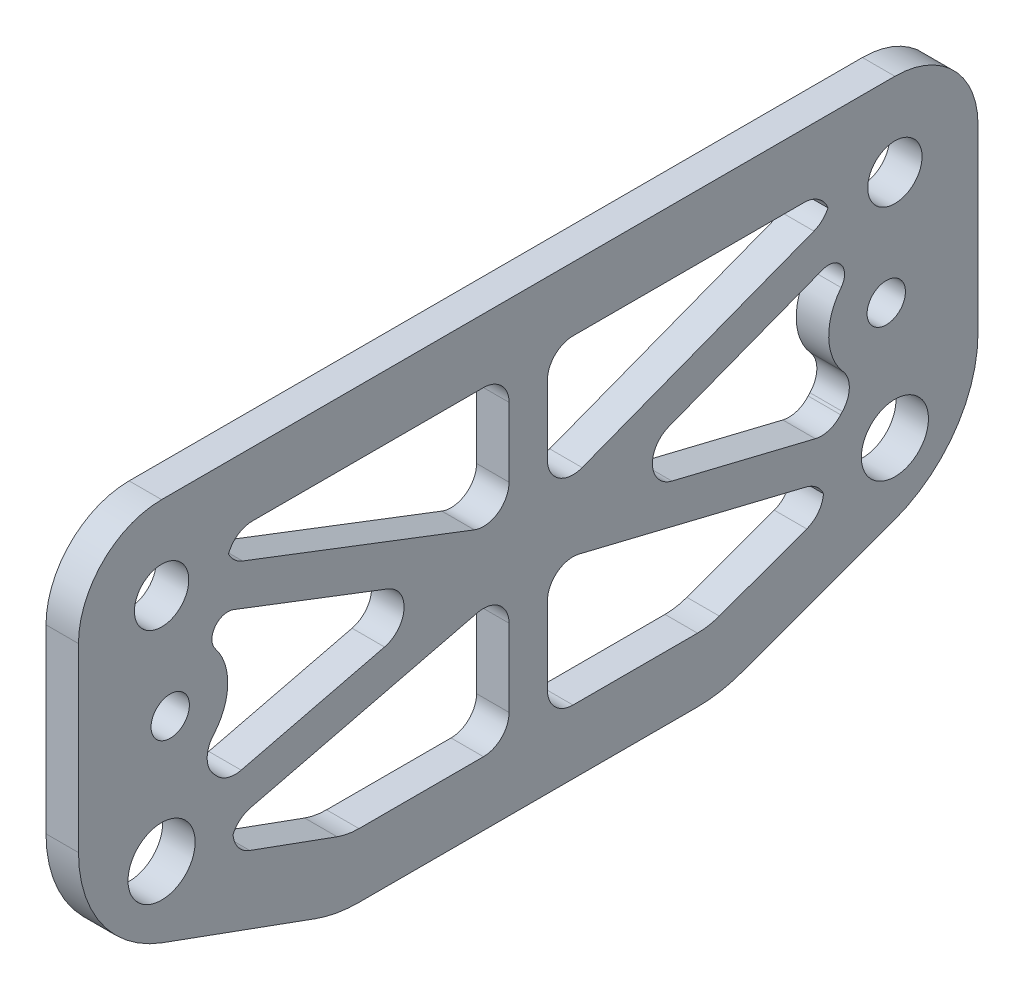
SolidWorks part; units mm, degrees
material "Acrylic (Medium-high impact)"
ref_plane "Front Plane" through (0, 0, 0) normal (0, 0, 1) x (1, 0, 0)
ref_plane "Top Plane" through (0, 0, 0) normal (0, 1, 0) x (1, 0, 0)
ref_plane "Right Plane" through (0, 0, 0) normal (1, 0, 0) x (0, 0, -1)
sketch "Sketch1" plane through (0, 0, 0) normal (1, 0, 0) x (0, 0, -1)
  line L0 (15, 17.5) -> (28.675, 17.5)
  line L1 (-15, -17.5) -> (15, -17.5)
  line L3 (-15, 17.5) -> (15, 17.5)
  line L5 (-15, -17.5) -> (15, 17.5) construction
  line L6 (-15, 17.5) -> (15, -17.5) construction
  line L8 (0, 17.5) -> (0, -17.5) construction
  line L10 (-15, 17.5) -> (-28.675, 17.5)
  line L11 (23.175, 171.1912) -> (23.175, -56.2088) construction
  line L13 (35.175, 11) -> (35.175, -3.1548)
  line L14 (28.5952, -12.5518) -> (15, -17.5)
  line L16 (-35.175, 11) -> (-35.175, -3.1548)
  line L17 (-28.5952, -12.5518) -> (-15, -17.5)
  arc A0 (28.675, 17.5) -> (35.175, 11) centre (28.675, 11) cw
  circle A1 centre (28.675, 11) radius 5.5 construction
  circle A2 centre (-28.675, 11) radius 5.5 construction
  arc A3 (-28.675, 17.5) -> (-35.175, 11) centre (-28.675, 11) ccw
  arc A4 (35.175, -3.1548) -> (28.5952, -12.5518) centre (25.175, -3.1548) cw
  circle A5 centre (28.675, 11) radius 2.125
  arc A6 (-35.175, -3.1548) -> (-28.5952, -12.5518) centre (-25.175, -3.1548) ccw
  circle A9 centre (-28.675, 11) radius 2.125
  circle A11 centre (28, 2.5) radius 1.5
  circle A12 centre (-28, 2.5) radius 1.5
  circle A13 centre (28.675, -7) radius 5.5 construction
  circle A14 centre (28.675, -7) radius 2.625
  circle A15 centre (-28.675, -7) radius 2.625
  circle A16 centre (-28.675, -7) radius 5.5 construction
  point P0 (0, 0)
  point P28 (0, 0)
  dimension "D1" = 11
  dimension "D2" = 1
  dimension "D3" = 4.25
  dimension "D4" = 3
  dimension "D6" = 20
  dimension "D8" = 10
  dimension "D11" = 5.25
  dimension "D12" = 11
  dimension "D5" = 35
  dimension "D7" = 30
  dimension "D9" = 28
  dimension "D10" = 8.5
  dimension "D13" = 9.5
extrude "Boss-Extrude1" add sketch "Sketch1" along normal blind 2.54
fillet "Fillet1" radius 10 2 edges at (1.27, -17.5, -15) (1.27, -17.5, 15)
sketch "Sketch2" plane through (0, 0, 0) normal (1, 0, 0) x (0, 0, -1)
  line L0 (-28.675, 11) -> (0, 0)
  line L5 (0, 12.5) -> (0, -12.5) construction
  line L7 (-28, 2.5) -> (0, 0)
  line L8 (0, 17.5) -> (0, -17.5) construction
  line L9 (-28.675, -7) -> (0, 0)
  line L10 (-29.0307, -5.5428) -> (-0.3557, 1.4572)
  line L11 (-28.3193, -8.4572) -> (0.3557, -1.4572)
  line L16 (-13.2367, -12.5) -> (13.2367, -12.5)
  line L17 (14.9468, -12.1985) -> (26.8851, -7.8533)
  line L18 (30.175, -3.1548) -> (30.175, 11)
  line L19 (28.675, 12.5) -> (-28.675, 12.5)
  line L20 (-30.175, 11) -> (-30.175, -3.1548)
  line L21 (-26.8851, -7.8533) -> (-14.9468, -12.1985)
  line L22 (-13.2367, -12.5) -> (13.2367, -12.5)
  line L23 (14.9468, -12.1985) -> (26.8851, -7.8533)
  line L24 (30.175, -3.1548) -> (30.175, 11)
  line L25 (28.675, 12.5) -> (-28.675, 12.5)
  line L26 (-30.175, 11) -> (-30.175, -3.1548)
  line L27 (-26.8851, -7.8533) -> (-14.9468, -12.1985)
  line L32 (0, -12.5) -> (0, 12.5) construction
  line L33 (0, 0) -> (0, -12.5)
  line L34 (-1.5, 12.5) -> (-1.5, -12.5)
  line L35 (1.5, 12.5) -> (1.5, -12.5)
  line L36 (-1.5, 12.5) -> (1.5, 12.5)
  line L37 (-1.5, -12.5) -> (1.5, -12.5)
  line L38 (-29.2122, 9.5995) -> (-0.5372, -1.4005)
  line L39 (-28.1378, 12.4005) -> (0.5372, 1.4005)
  line L40 (28.675, -7) -> (0, 0)
  line L41 (28.3193, -8.4572) -> (-0.3557, -1.4572)
  line L42 (28.1378, 12.4005) -> (-0.5372, 1.4005)
  line L43 (29.0307, -5.5428) -> (0.3557, 1.4572)
  line L44 (29.2122, 9.5995) -> (0.5372, -1.4005)
  line L45 (28.675, 11) -> (0, 0)
  arc A1 (23.0409, 7.2321) -> (24.4693, 5.29) centre (23.4886, 6.065) cw
  circle A2 centre (-28, 2.5) radius 4.5
  circle A3 centre (-28, 2.5) radius 4.5
  arc A4 (-23.0409, 7.2321) -> (-24.4693, 5.29) centre (-23.4886, 6.065) ccw
  circle A5 centre (28, 2.5) radius 4.5
  circle A6 centre (28, 2.5) radius 4.5
  circle A10 centre (28.675, -7) radius 5.625
  circle A11 centre (-28.675, 11) radius 5.125
  arc A12 (13.2367, -12.5) -> (14.9468, -12.1985) centre (13.2367, -7.5) ccw
  arc A13 (26.8851, -7.8533) -> (30.175, -3.1548) centre (25.175, -3.1548) ccw
  arc A14 (30.175, 11) -> (28.675, 12.5) centre (28.675, 11) ccw
  arc A15 (-28.675, 12.5) -> (-30.175, 11) centre (-28.675, 11) ccw
  arc A16 (-30.175, -3.1548) -> (-26.8851, -7.8533) centre (-25.175, -3.1548) ccw
  arc A17 (-14.9468, -12.1985) -> (-13.2367, -12.5) centre (-13.2367, -7.5) ccw
  arc A18 (13.2367, -12.5) -> (14.9468, -12.1985) centre (13.2367, -7.5) ccw
  arc A19 (26.8851, -7.8533) -> (30.175, -3.1548) centre (25.175, -3.1548) ccw
  arc A20 (30.175, 11) -> (28.675, 12.5) centre (28.675, 11) ccw
  arc A21 (-28.675, 12.5) -> (-30.175, 11) centre (-28.675, 11) ccw
  arc A22 (-30.175, -3.1548) -> (-26.8851, -7.8533) centre (-25.175, -3.1548) ccw
  arc A23 (-14.9468, -12.1985) -> (-13.2367, -12.5) centre (-13.2367, -7.5) ccw
  circle A24 centre (-28.675, 11) radius 5.125
  circle A25 centre (28.675, -7) radius 5.625
  circle A26 centre (28.675, 11) radius 5.125
  circle A27 centre (28.675, 11) radius 5.125
  circle A31 centre (-28.675, -7) radius 5.625
  circle A32 centre (-28.675, -7) radius 5.625
  dimension "D10" = 1.5
  dimension "D11" = 3
  dimension "D12" = 1.25
  dimension "D1" = 5
  dimension "D3" = 3
  dimension "D4" = 3
  dimension "D5" = 3
  dimension "D6" = 3
  dimension "D7" = 1.5
  dimension "D8" = 1.5
  dimension "D9" = 1.5
  dimension "D13" = 1.5
  dimension "D14" = 1.5
  dimension "D15" = 3
extrude "Cut-Extrude2" cut sketch "Sketch2" along normal through all contours A25 L41 L35 L22 A18 L23 | A32 L27 A23 L22 L34 L11 | A27 L44 L43 A25 A6 | A24 A3 L7 L38 | A32 L10 L38 L7 A3 | A24 L39 L34 L25 | A27 L25 L35 L42
fillet "Fillet2" radius 2 22 edges at (1.27, -12.5, -1.5) (1.27, -12.5, 1.5) (1.27, -1.9102, -1.5) (1.27, -9.101, -23.4571) (1.27, -7.1715, -23.0526) (1.27, 12.5, -1.5) (1.27, 2.182, -1.5) (1.27, 10.6453, -23.5623) (1.27, 12.5, -23.7744) (1.27, -7.1715, 23.0526) (1.27, -9.101, 23.4571) (1.27, 0.3188, -5.0191) (1.27, -4.2571, -23.7641) (1.27, -1.7744, -26.5932) (1.27, -1.7744, 26.5932) (1.27, -4.2571, 23.7641) (1.27, 0.3188, 5.0191) (1.27, -1.9102, 1.5) (1.27, 12.5, 1.5) (1.27, 12.5, 23.7744) (1.27, 10.6453, 23.5623) (1.27, 2.182, 1.5)
